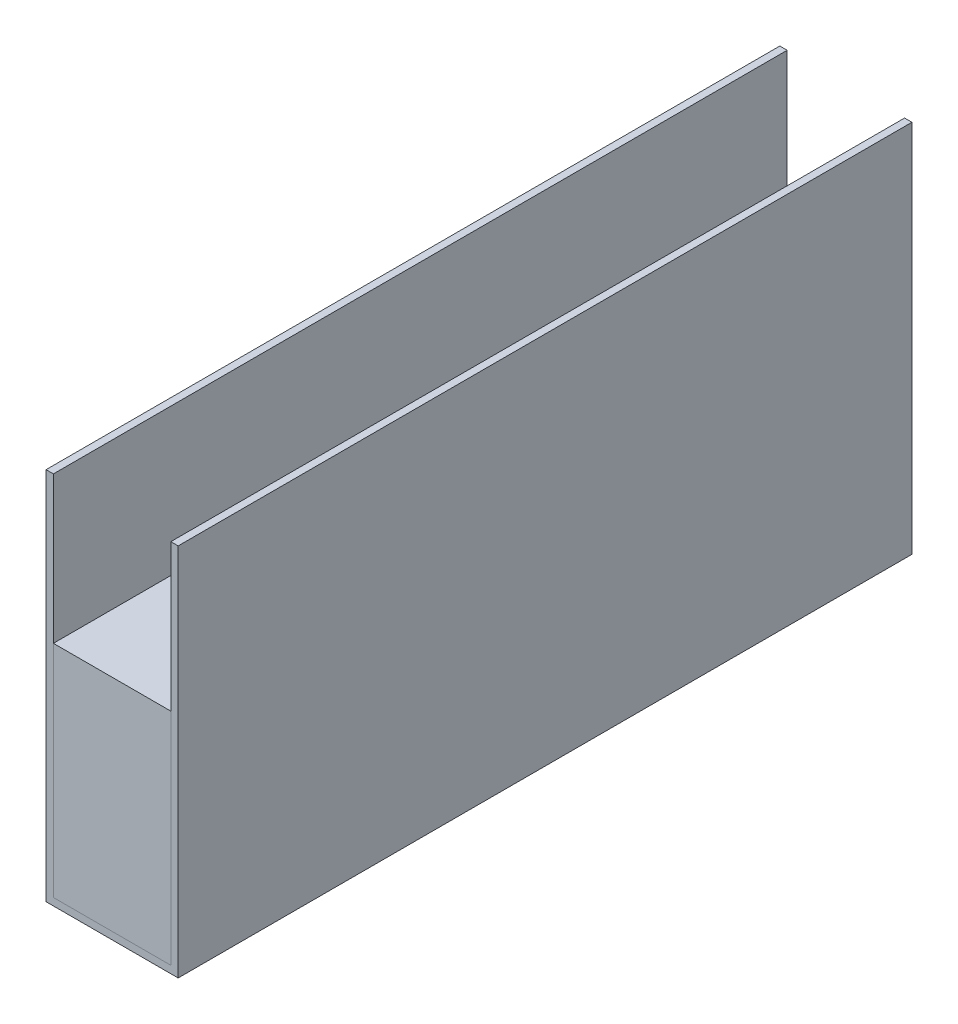
SolidWorks part; units mm, degrees
ref_plane "Front Plane" through (0, 0, 0) normal (0, 0, 1) x (1, 0, 0)
ref_plane "Top Plane" through (0, 0, 0) normal (0, 1, 0) x (1, 0, 0)
ref_plane "Right Plane" through (0, 0, 0) normal (1, 0, 0) x (0, 0, -1)
sketch "Sketch1" plane through (0, 0, 0) normal (0, 0, 1) x (1, 0, 0)
  line L0 (45, 125) -> (45, -130)
  line L2 (-40, 125) -> (-40, -125)
  line L3 (-40, -125) -> (40, -125)
  line L4 (40, 125) -> (40, -125)
  line L5 (0, -125) -> (0, 125) construction
  line L6 (-40, 0) -> (40, 0) construction
  line L7 (-45, -130) -> (45, -130)
  line L8 (-45, 125) -> (-45, -130)
  line L10 (-52.402, 125) -> (-40, 125) construction
  line L11 (45, 130) -> (45, -130) construction
  line L12 (-45, 130) -> (-45, -130) construction
  line L13 (-45, 130) -> (45, 130) construction
  line L14 (-45, 125) -> (-40, 125)
  line L15 (40, 125) -> (45, 125)
  line L16 (-40, 125) -> (40, 125) construction
  line L17 (40, 125) -> (52.402, 125) construction
  line L19 (-40, -125) -> (40, -125)
  line L20 (-40, -125) -> (-40, 25)
  line L21 (-40, 25) -> (40, 25)
  line L22 (40, -125) -> (40, 25)
  point P0 (0, 0)
  point P14 (-20, 125)
  dimension "D1" = 250
  dimension "D2" = 80
  dimension "D3" = 5
  dimension "D4" = 150
  dimension "D5" = 80
extrude "Boss-Extrude1" add sketch "Sketch1" along normal blind 500 contours L2 L14 L8 L7 L0 L15 L4 L3
extrude "Boss-Extrude3" add sketch "Sketch1<4>" along normal blind 500 separate body contours L21 L2 L3 L4 region at (0, -50, 0)
sketch "Sketch1<4>" plane through (0, 0, 0) normal (0, 0, 1) x (1, 0, 0) same geometry as "Sketch1"
